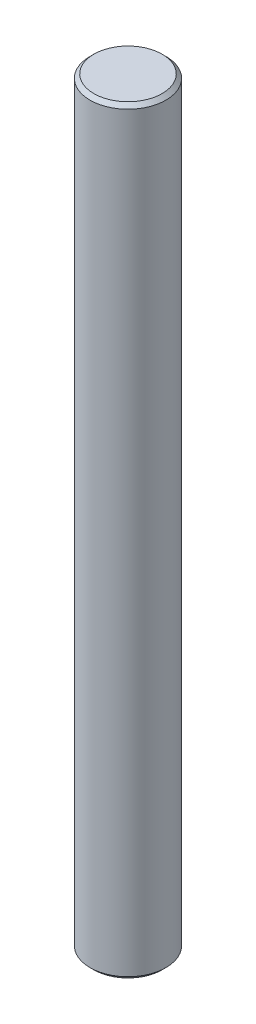
SolidWorks part; units mm, degrees
ref_plane "Front Plane" through (0, 0, 0) normal (0, 0, 1) x (1, 0, 0)
ref_plane "Top Plane" through (0, 0, 0) normal (0, 1, 0) x (1, 0, 0)
ref_plane "Right Plane" through (0, 0, 0) normal (1, 0, 0) x (0, 0, -1)
sketch "MainSketch" plane through (0, 0, 0) normal (0, 1, 0) x (1, 0, 0)
  circle A0 centre (0, 0) radius 5
  dimension "D1" = 10
extrude "Boss-Extrude1" add sketch "MainSketch" along normal blind 100
chamfer "Chamfer1" distance 0.5 angle 45 2 edges at (0, 100, 5) (0, 0, 5)
